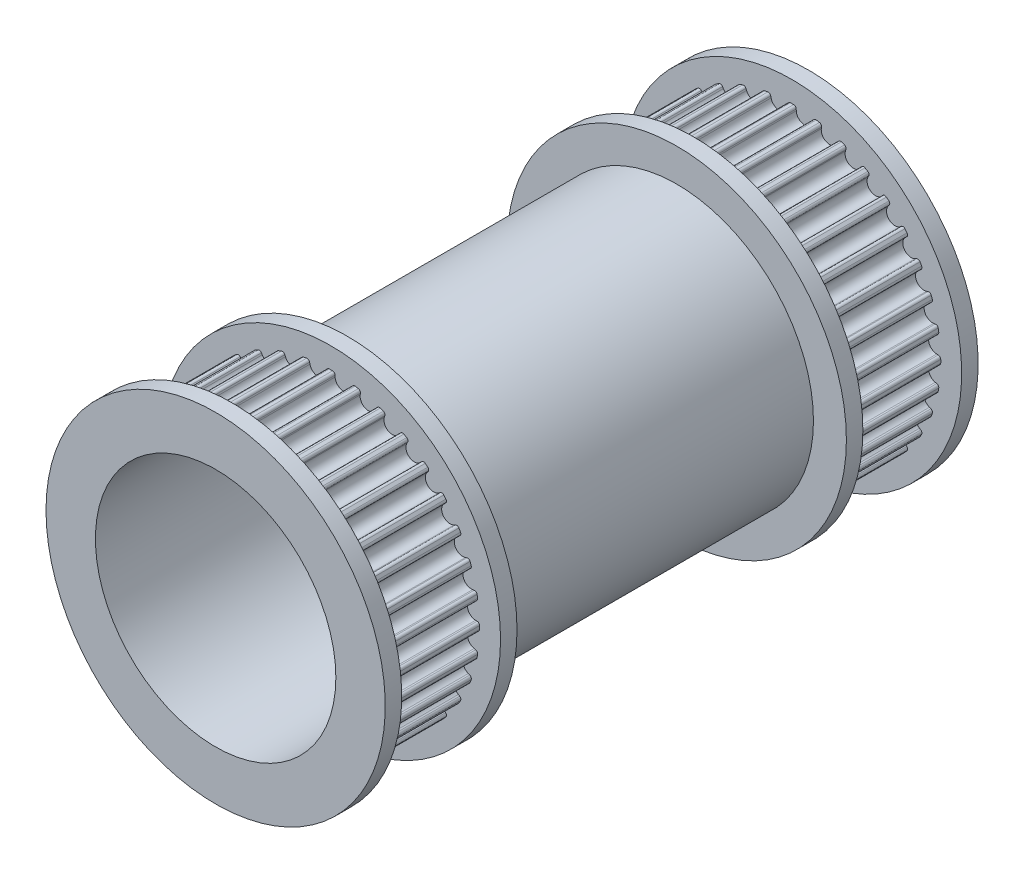
SolidWorks part; units mm, degrees
ref_plane "前视基准面" through (0, 0, 0) normal (0, 0, 1) x (1, 0, 0)
ref_plane "上视基准面" through (0, 0, 0) normal (0, 1, 0) x (1, 0, 0)
ref_plane "右视基准面" through (0, 0, 0) normal (1, 0, 0) x (0, 0, -1)
sketch "Sketch2" plane through (0, 0, 0) normal (0, 0, 1) x (1, 0, 0)
  circle A0 centre (0, 0) radius 45.15
  dimension "D1" = 90.3
extrude "Extrude1" add sketch "Sketch2" along normal blind 30
sketch "Sketch1" plane through (0, 0, 0) normal (0, 0, 1) x (1, 0, 0)
  line L0 (0, 0) -> (0, 45.835) construction
  line L1 (0, 0) -> (-3.9948, 45.6606) construction
  line L2 (-1.2656, 44.3946) -> (-1.2821, 43.9222)
  line L3 (-6.4627, 43.9399) -> (-6.3644, 43.4775)
  circle A0 centre (0, 0) radius 45.835 construction
  arc A1 (-0.4946, 45.1473) -> (-7.3526, 44.5473) centre (0, 0) ccw
  arc A2 (-6.3644, 43.4775) -> (-1.2821, 43.9222) centre (-3.8505, 44.0119) ccw
  arc A3 (-0.4946, 45.1473) -> (-1.2656, 44.3946) centre (-0.4861, 44.3673) ccw
  arc A4 (-7.3526, 44.5473) -> (-6.4627, 43.9399) centre (-7.2256, 43.7777) cw
  point P4 (45.6606, 3.9948)
  point P5 (44.2732, 11.863)
  point P6 (41.5406, 19.3707)
  point P7 (37.5458, 26.2899)
  point P8 (32.4102, 32.4102)
  point P9 (26.2899, 37.5458)
  point P10 (19.3707, 41.5406)
  point P11 (11.863, 44.2732)
  point P12 (3.9948, 45.6606)
  point P13 (-3.9948, 45.6606)
  point P14 (-11.863, 44.2732)
  point P15 (-19.3707, 41.5406)
  point P16 (-26.2899, 37.5458)
  point P17 (-32.4102, 32.4102)
  point P18 (-37.5458, 26.2899)
  point P19 (-41.5406, 19.3707)
  point P20 (-44.2732, 11.863)
  point P21 (-45.6606, 3.9948)
  point P22 (-45.6606, -3.9948)
  point P23 (-44.2732, -11.863)
  point P24 (-41.5406, -19.3707)
  point P25 (-37.5458, -26.2899)
  point P26 (-32.4102, -32.4102)
  point P27 (-26.2899, -37.5458)
  point P28 (-19.3707, -41.5406)
  point P29 (-11.863, -44.2732)
  point P30 (-3.9948, -45.6606)
  point P31 (3.9948, -45.6606)
  point P32 (11.863, -44.2732)
  point P33 (19.3707, -41.5406)
  point P34 (26.2899, -37.5458)
  point P35 (32.4102, -32.4102)
  point P36 (37.5458, -26.2899)
  point P37 (41.5406, -19.3707)
  point P38 (44.2732, -11.863)
  point P39 (45.6606, -3.9948)
  dimension "D1" = 91.67
  dimension "D2" = 90.3
  dimension "D3" = 5.14
  dimension "D4" = 3.54
  dimension "D5" = 1.56
  dimension "D6" = 7
extrude "Extrude2" cut sketch "Sketch1" along normal up to surface (30 mm away) up to face at (45.15, 0, 30)
pattern_circular "CirPattern1" count 36 over 360 about axis through (0, 0, 30) along (0, 0, 1) of "Extrude2"
sketch "Sketch6" plane through (0, 0, 30) normal (0, 0, 1) x (1, 0, 0)
  circle A0 centre (0, 0) radius 41.5
  dimension "D1" = 83
extrude "Extrude6" add sketch "Sketch6" along normal blind 110
ref_plane "Plane2" through (0, 0, 85) normal (0, 0, 1) x (1, 0, 0)
mirror "Mirror4" about plane through (0, 0, 85) normal (0, 0, 1) of "CirPattern1", "Extrude2", "Extrude1"
sketch "Sketch7" plane through (0, 0, 30) normal (0, 0, 1) x (1, 0, 0)
  circle A0 centre (0, 0) radius 41.5 construction
  circle A1 centre (0, 0) radius 41.5
  circle A2 centre (0, 0) radius 51.5
  dimension "D1" = 103
extrude "Extrude7" add sketch "Sketch7" along normal blind 5
sketch "Sketch8" plane through (0, 0, 0) normal (0, 0, -1) x (-1, 0, 0)
  circle A0 centre (0, 0) radius 51.5
  dimension "D1" = 103
extrude "Extrude8" add sketch "Sketch8" along normal blind 5
mirror "Mirror5" about plane through (0, 0, 85) normal (0, 0, 1) of "Extrude8", "Extrude7"
sketch "Sketch9" plane through (0, 0, 85) normal (0, 0, 1) x (1, 0, 0)
  circle A0 centre (0, 0) radius 36.5
  dimension "D1" = 73
extrude "Extrude9" cut sketch "Sketch9" against normal through all both and the other way through all
ref_plane "Plane3" through (0, 0, 15) normal (0, 0, 1) x (1, 0, 0)
